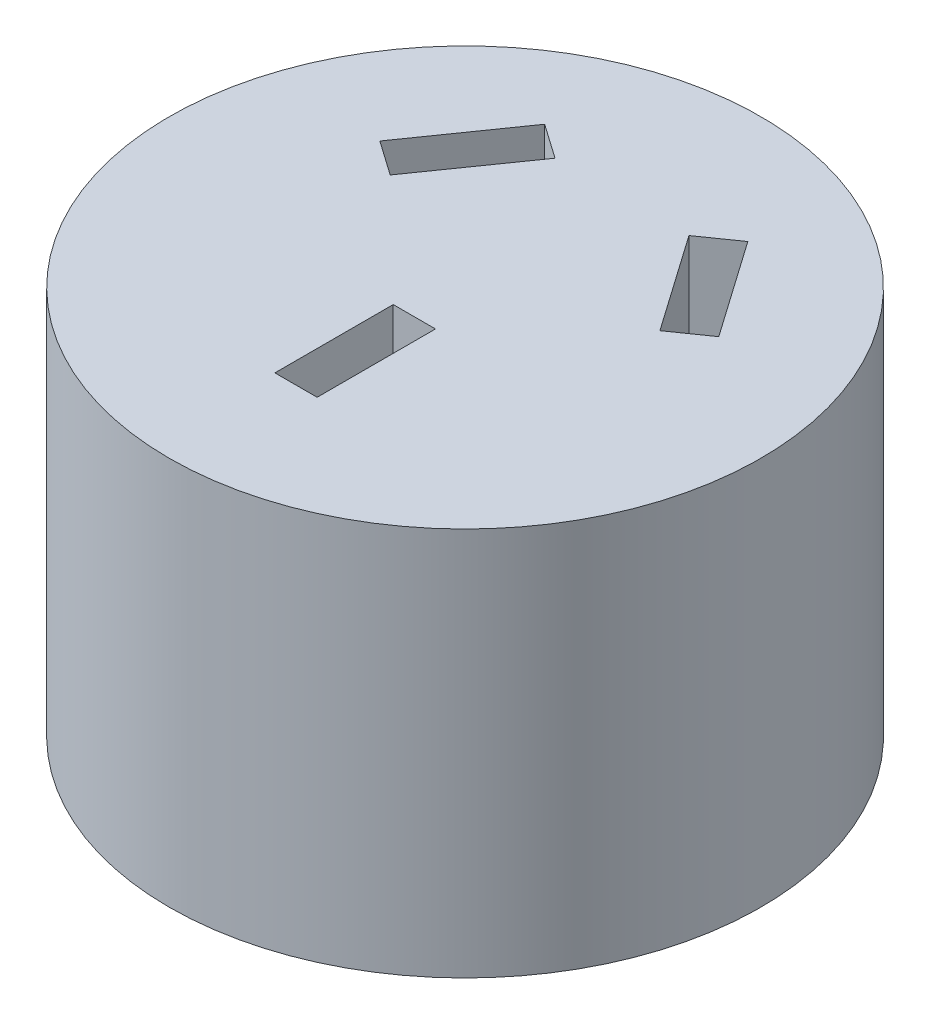
SolidWorks part; units mm, degrees
ref_plane "Front Plane" through (0, 0, 0) normal (0, 0, 1) x (1, 0, 0)
ref_plane "Top Plane" through (0, 0, 0) normal (0, 1, 0) x (1, 0, 0)
ref_plane "Right Plane" through (0, 0, 0) normal (1, 0, 0) x (0, 0, -1)
sketch "Croquis1" plane through (0, 0, 0) normal (0, 1, 0) x (1, 0, 0)
  circle A0 centre (0, 0) radius 17.5
  dimension "D1" = 35
extrude "Saliente-Extruir1" add sketch "Croquis1" along normal blind 11.5 and the other way blind 11.5
sketch "Croquis2" plane through (0, 11.5, 0) normal (0, 1, 0) x (1, 0, 0)
  line L0 (0, -10) -> (0, -3)
  line L1 (-9, 4.2659) -> (-4.985, 10)
  line L2 (-4.985, 10) -> (4.985, 10) construction
  line L3 (4.985, 10) -> (9, 4.2659)
  line L4 (9, 4.2659) -> (-9, 4.2659) construction
  line L5 (0, -10) -> (0, 10) construction
  point P5 (0, 10)
  point P8 (0, 4.2659)
  point P11 (0, 0)
  dimension "D1" = 70
  dimension "D2" = 18
  dimension "D4" = 20
  dimension "D5" = 7
extrude "Cortar-Extruir-Lámina1" cut sketch "Croquis2" against normal through all thin thin type mid plane wall 2.5
hole_wizard "Taladro2" positions "Croquis3" profile "Croquis4" legacy
sketch "Croquis3" plane through (0, -11.5, 0) normal (0, -1, 0) x (-1, 0, 0)
  line L1 (-10, -3) -> (10, -3) construction
  point P3 (-10, -3)
  point P4 (10, -3)
  point P6 (0, -3)
  dimension "D1" = 3
  dimension "D2" = 20
sketch "Croquis4" plane through (10, -11.5, 3) normal (1, 0, 0) x (0, 0, -1)
  line L0 (0, 0) -> (0, 7)
  line L1 (0, 7) -> (2.8, 7)
  line L2 (2.8, 7) -> (2.8, 0)
  line L3 (2.8, 0) -> (0, 0)
  line L4 (0, 110) -> (0, -10) construction
  dimension "Diámetro" = 5.6
  dimension "Profundidad" = 7
hole_wizard "Taladro3" positions "Croquis3D2" profile "Croquis35" legacy
sketch3d "Croquis3D2"
  point P0 (-15.907, 1.6651, 7.295)
sketch "Croquis35" plane through (-15.907, 1.6651, 7.295) normal (0, 1, 0) x (0.4169, 0, 0.909)
  line L0 (0, 0) -> (0, 15)
  line L1 (0, 15) -> (1.5, 15)
  line L2 (1.5, 15) -> (1.5, 5)
  line L3 (1.5, 5) -> (5, 5)
  line L4 (5, 5) -> (5, 0)
  line L5 (5, 0) -> (0, 0)
  line L6 (0, 110) -> (0, -10) construction
  dimension "Diámetro" = 3
  dimension "Profundidad" = 15
  dimension "Diámetro de refrentado 1" = 10
  dimension "Profundidad de refrentado 1" = 5
